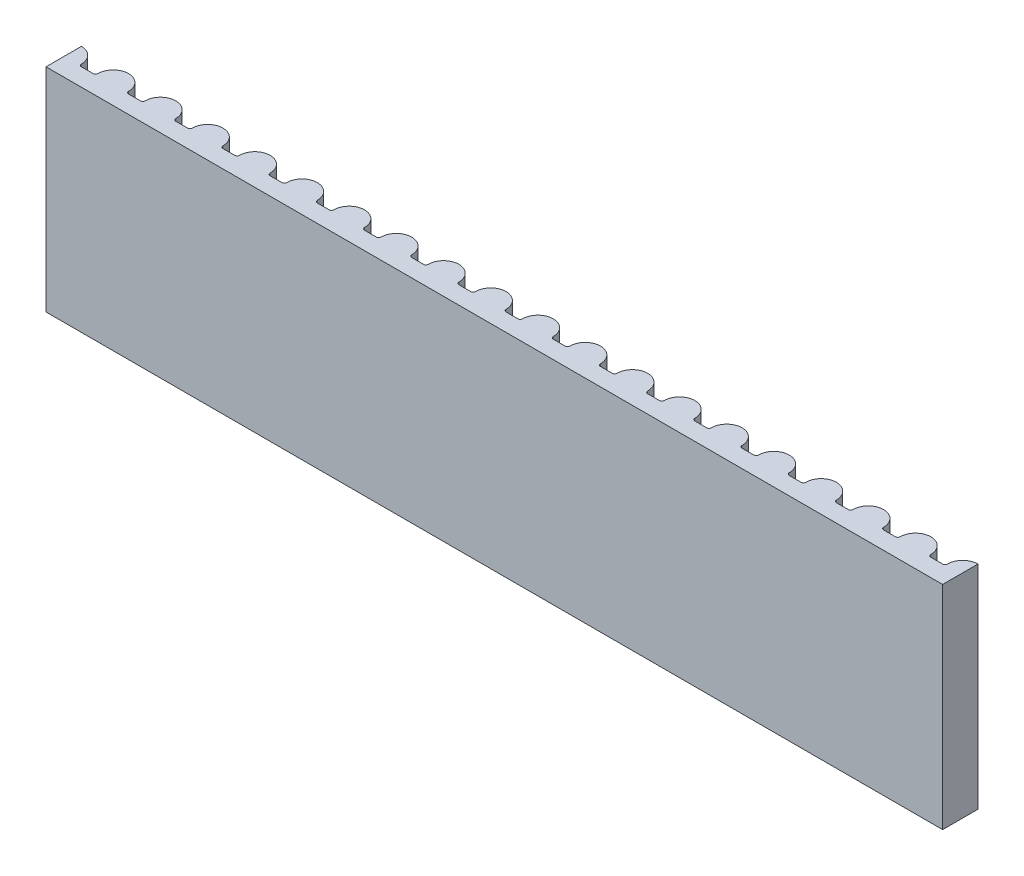
SolidWorks part; units mm, degrees
ref_plane "Front Plane" through (0, 0, 0) normal (0, 0, 1) x (1, 0, 0)
ref_plane "Top Plane" through (0, 0, 0) normal (0, 1, 0) x (1, 0, 0)
ref_plane "Right Plane" through (0, 0, 0) normal (1, 0, 0) x (0, 0, -1)
sketch "Sketch1" plane through (0, 0, 0) normal (0, 1, 0) x (1, 0, 0)
  line L0 (0, 0) -> (1, 0)
  line L1 (1, 0) -> (1, 1.5)
  line L2 (1, 1.5) -> (0.35, 1.5) construction
  line L3 (0.35, 1.5) -> (0.35, 0.75) construction
  line L4 (0.35, 0.75) -> (0, 0.75) construction
  line L5 (0, 0.75) -> (0, 0)
  line L6 (0.25, 0.75) -> (0, 0.75)
  arc A0 (1, 1.5) -> (0.35, 0.85) centre (1, 0.85) ccw
  arc A1 (0.25, 0.75) -> (0.35, 0.85) centre (0.25, 0.85) ccw
  dimension "D1" = 0.75
  dimension "D2" = 1.5
  dimension "D3" = 1
  dimension "D4" = 0.35
extrude "Boss-Extrude1" add sketch "Sketch1" along normal mid plane 9
mirror "Mirror1" about plane through (0, 4.5, -0.75) normal (1, 0, 0) of "Boss-Extrude1"
pattern_linear "LPattern2" count 10 spacing 2 along (1, 0, 0) of bodies 102
pattern_linear "LPattern3" count 10 spacing 2 along (-1, 0, 0) of bodies 102
combine bodies "Combine1" operation type add bodies to combine 102 103 104 105 106 107 108 109 110 111 112 113 114 115 116 117 118 119 120
